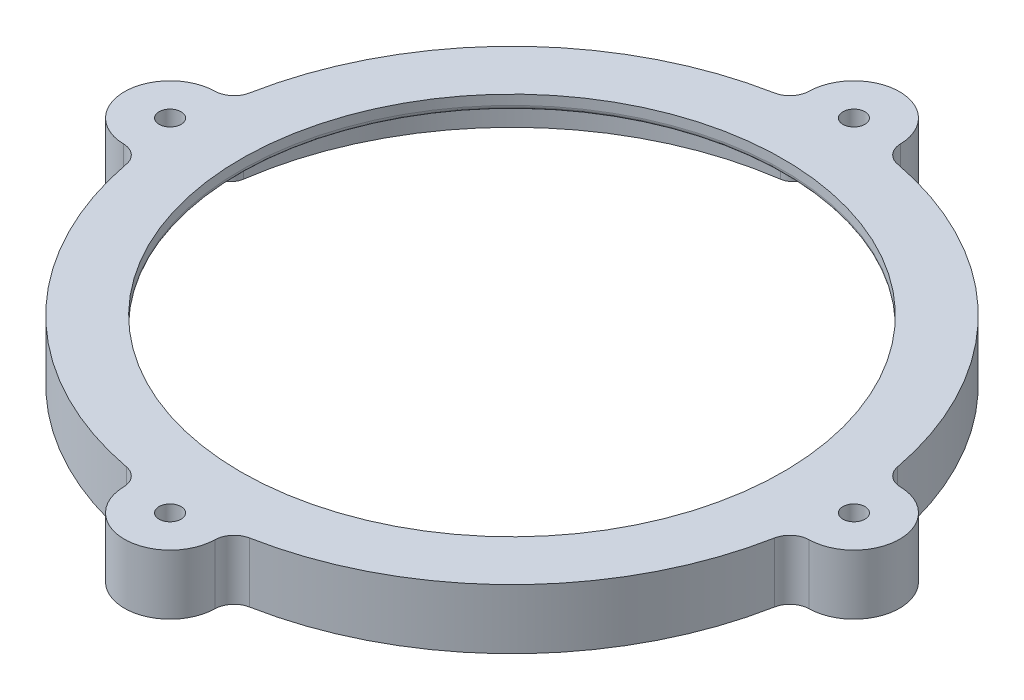
SolidWorks part; units mm, degrees
ref_plane "Front Plane" through (0, 0, 0) normal (0, 0, 1) x (1, 0, 0)
ref_plane "Top Plane" through (0, 0, 0) normal (0, 1, 0) x (1, 0, 0)
ref_plane "Right Plane" through (0, 0, 0) normal (1, 0, 0) x (0, 0, -1)
sketch "Sketch1" plane through (0, 0, 0) normal (0, 0, 1) x (1, 0, 0)
  line L0 (64.5, 0) -> (64.5, 1.75)
  line L1 (64.5, 1.75) -> (55.5, 1.75)
  line L2 (55.5, 1.75) -> (55.5, 4.75)
  line L3 (55.5, 4.75) -> (67.5, 4.75)
  line L4 (67.5, 4.75) -> (67.5, 0)
  line L5 (67.5, 0) -> (64.5, 0)
  line L6 (0, 4.75) -> (0, 0) construction
  dimension "D1" = 3
  dimension "D2" = 3
  dimension "D3" = 55.5
  dimension "D4" = 1.75
  dimension "D5" = 64.5
revolve "Revolve1" add sketch "Sketch1" angle 360 about L6
fillet "Fillet1" radius 1 1 edges at (0, 1.75, 55.5)
sketch "Sketch2" plane through (0, 4.75, 0) normal (0, 1, 0) x (1, 0, 0)
  line L0 (0, 0) -> (70, 0) construction
  line L1 (67.2328, 6) -> (70, 6)
  line L2 (70, -6) -> (67.2328, -6)
  line L3 (67.2328, -6) -> (67.2328, 6)
  circle A0 centre (0, 0) radius 67.5 construction
  arc A1 (70, 6) -> (70, -6) centre (70, 0) cw
  dimension "D1" = 6
  dimension "D2" = 70
extrude "Boss-Extrude1" add sketch "Sketch2" against normal up to surface (4.75 mm away) up to face at (0, 0, 67.5)
fillet "Fillet2" radius 2 2 edges at (67.2328, 2.375, 6) (67.2328, 2.375, -6)
hole_wizard "M4 Clearance Hole1" positions "Sketch7" profile "Sketch8" hole size "M4" standard "ANSI Metric" end condition through all
sketch "Sketch7" plane through (0, 4.75, 0) normal (0, 1, 0) x (1, 0, 0)
  point P0 (70, 0)
sketch "Sketch8" plane through (70, 4.75, 0) normal (1, 0, 0) x (0, 0, 1)
  line L0 (0, 0) -> (0, 4.75)
  line L1 (0, 4.75) -> (2.25, 4.75)
  line L2 (2.25, 4.75) -> (2.25, 0)
  line L5 (2.25, 0) -> (0, 0)
  line L11 (0, -6.35) -> (0, 107.95) construction
  dimension "Thru Hole Dia." = 4.5
  dimension "Thru Hole Depth" = 4.75
pattern_circular "CirPattern3" count 4 over 360 about axis through (0, 0, 0) along (0, 1, 0) of "Boss-Extrude1", "Fillet2", "M4 Clearance Hole1"
sketch "Sketch9" plane through (0, 0, 0) normal (0, -1, 0) x (1, 0, 0)
  line L4 (6, 69.038) -> (6, 70) construction
  line L11 (6.35, 70) -> (6.35, 64.1867)
  line L12 (-6.35, 70) -> (-6.35, 64.1867)
  line L13 (9.35, 70) -> (9.35, 66.8493)
  line L14 (-9.35, 70) -> (-9.35, 66.8493)
  line L15 (-70, 9.35) -> (-66.8493, 9.35)
  line L16 (-70, -9.35) -> (-66.8493, -9.35)
  line L19 (70, -9.35) -> (66.8493, -9.35)
  line L20 (70, 9.35) -> (66.8493, 9.35)
  line L23 (9.35, -70) -> (9.35, -66.8493)
  line L24 (-9.35, -70) -> (-9.35, -66.8493)
  line L56 (6.35, 69.038) -> (6.35, 70)
  line L57 (-6.35, 70) -> (-6.35, 69.038)
  line L58 (-69.038, 6.35) -> (-70, 6.35)
  line L59 (-70, -6.35) -> (-69.038, -6.35)
  line L60 (-6.35, -69.038) -> (-6.35, -70)
  line L61 (6.35, -70) -> (6.35, -69.038)
  line L62 (69.038, -6.35) -> (70, -6.35)
  line L63 (70, 6.35) -> (69.038, 6.35)
  line L66 (-64.1867, 6.35) -> (-70, 6.35)
  line L67 (-70, -6.35) -> (-64.1867, -6.35)
  line L68 (-6.35, -64.1867) -> (-6.35, -70)
  line L69 (6.35, -70) -> (6.35, -64.1867)
  line L70 (64.1867, -6.35) -> (70, -6.35)
  line L71 (70, 6.35) -> (64.1867, 6.35)
  arc A0 (7.7698, -67.0513) -> (67.0513, -7.7698) centre (0, 0) ccw construction
  arc A1 (67.0513, 7.7698) -> (7.7698, 67.0513) centre (0, 0) ccw construction
  arc A2 (66.8493, 9.35) -> (9.35, 66.8493) centre (0, 0) ccw
  arc A3 (-7.4245, -64.0713) -> (-6.35, -64.1867) centre (0, 0) ccw
  arc A4 (-9.35, 66.8493) -> (-66.8493, 9.35) centre (0, 0) ccw
  arc A5 (-66.8493, -9.35) -> (-9.35, -66.8493) centre (0, 0) ccw
  arc A7 (9.35, -66.8493) -> (66.8493, -9.35) centre (0, 0) ccw
  arc A8 (-64.0713, -7.4245) -> (-7.4245, -64.0713) centre (0, 0) ccw
  arc A13 (-67.0513, -7.7698) -> (-7.7698, -67.0513) centre (0, 0) ccw construction
  arc A14 (7.4245, 64.0713) -> (6.35, 64.1867) centre (0, 0) ccw
  arc A15 (-7.7698, 67.0513) -> (-67.0513, 7.7698) centre (0, 0) ccw construction
  arc A16 (64.1867, 6.35) -> (64.0713, 7.4245) centre (0, 0) ccw
  arc A17 (-6.35, 64.1867) -> (-64.1867, 6.35) centre (0, 0) ccw
  arc A18 (6.35, -64.1867) -> (64.1867, -6.35) centre (0, 0) ccw
  arc A19 (-64.1867, -6.35) -> (-64.0713, -7.4245) centre (0, 0) ccw
  arc A45 (9.35, 70) -> (-9.35, 70) centre (0, 70) ccw
  arc A46 (-70, 9.35) -> (-70, -9.35) centre (-70, 0) ccw
  arc A47 (-9.35, -70) -> (9.35, -70) centre (0, -70) ccw
  arc A48 (70, -9.35) -> (70, 9.35) centre (70, 0) ccw
  circle A49 centre (0, 0) radius 64.5 construction
  arc A50 (64.0713, 7.4245) -> (7.4245, 64.0713) centre (0, 0) ccw
  arc A61 (67.399, 7.8101) -> (7.8101, 67.399) centre (0, 0) ccw
  arc A62 (6.35, 69.038) -> (7.8101, 67.399) centre (8, 69.038) ccw
  arc A63 (6.35, 70) -> (-6.35, 70) centre (0, 70) ccw
  arc A64 (-7.8101, 67.399) -> (-6.35, 69.038) centre (-8, 69.038) ccw
  arc A65 (-7.8101, 67.399) -> (-67.399, 7.8101) centre (0, 0) ccw
  arc A66 (-69.038, 6.35) -> (-67.399, 7.8101) centre (-69.038, 8) ccw
  arc A67 (-70, 6.35) -> (-70, -6.35) centre (-70, 0) ccw
  arc A68 (-67.399, -7.8101) -> (-69.038, -6.35) centre (-69.038, -8) ccw
  arc A69 (-67.399, -7.8101) -> (-7.8101, -67.399) centre (0, 0) ccw
  arc A70 (-6.35, -69.038) -> (-7.8101, -67.399) centre (-8, -69.038) ccw
  arc A71 (-6.35, -70) -> (6.35, -70) centre (0, -70) ccw
  arc A72 (7.8101, -67.399) -> (6.35, -69.038) centre (8, -69.038) ccw
  arc A73 (7.8101, -67.399) -> (67.399, -7.8101) centre (0, 0) ccw
  arc A74 (69.038, -6.35) -> (67.399, -7.8101) centre (69.038, -8) ccw
  arc A75 (70, -6.35) -> (70, 6.35) centre (70, 0) ccw
  arc A76 (67.399, 7.8101) -> (69.038, 6.35) centre (69.038, 8) ccw
  arc A79 (6.35, 70) -> (-6.35, 70) centre (0, 70) ccw
  arc A83 (-70, 6.35) -> (-70, -6.35) centre (-70, 0) ccw
  arc A87 (-6.35, -70) -> (6.35, -70) centre (0, -70) ccw
  arc A91 (70, -6.35) -> (70, 6.35) centre (70, 0) ccw
  dimension "D3" = 1.4245
  dimension "D4" = 58.0713
  dimension "D5" = 13.4245
  dimension "D6" = 70.0713
  dimension "D1" = 0.35
  dimension "D2" = 3
extrude "Boss-Extrude2" add sketch "Sketch9" along normal up to vertex
sketch "Sketch10" plane through (0, 4.75, 0) normal (0, 1, 0) x (1, 0, 0)
  line L6 (9.35, -70) -> (9.35, -66.8493)
  line L8 (6.35, -67.9078) -> (6.35, -70)
  line L9 (-6.35, -70) -> (-6.35, -67.9078)
  line L11 (-9.35, -66.8493) -> (-9.35, -70)
  line L12 (9.35, -70) -> (9.35, -66.8493)
  line L17 (-9.35, -66.8493) -> (-9.35, -70)
  line L18 (-70, -9.35) -> (-66.8493, -9.35)
  line L20 (-67.9078, -6.35) -> (-70, -6.35)
  line L21 (-70, 6.35) -> (-67.9078, 6.35)
  line L23 (-66.8493, 9.35) -> (-70, 9.35)
  line L24 (-70, -9.35) -> (-66.8493, -9.35)
  line L29 (-66.8493, 9.35) -> (-70, 9.35)
  line L31 (66.8493, -9.35) -> (70, -9.35)
  line L32 (70, 9.35) -> (66.8493, 9.35)
  line L34 (67.9078, 6.35) -> (70, 6.35)
  line L35 (70, -6.35) -> (67.9078, -6.35)
  line L37 (66.8493, -9.35) -> (70, -9.35)
  line L38 (70, 9.35) -> (66.8493, 9.35)
  line L42 (-9.35, 70) -> (-9.35, 66.8493)
  line L44 (-6.35, 67.9078) -> (-6.35, 70)
  line L45 (6.35, 70) -> (6.35, 67.9078)
  line L47 (9.35, 66.8493) -> (9.35, 70)
  line L48 (-9.35, 70) -> (-9.35, 66.8493)
  line L53 (9.35, 66.8493) -> (9.35, 70)
  circle A0 centre (0, 70) radius 2.25 construction
  circle A1 centre (-70, 0) radius 2.25 construction
  circle A2 centre (70, 0) radius 2.25 construction
  circle A3 centre (0, -70) radius 2.25 construction
  circle A4 centre (0, 70) radius 2.25
  circle A5 centre (-70, 0) radius 2.25
  arc A6 (7.7698, -67.0513) -> (9.35, -66.8493) centre (0, 0) ccw
  arc A7 (-6.35, -67.9078) -> (-7.7698, -67.0513) centre (-8, -69.038) ccw
  arc A8 (-6.35, -70) -> (6.35, -70) centre (0, -70) ccw
  arc A9 (-6.35, -67.9078) -> (-7.7698, -67.0513) centre (-8, -69.038) ccw
  arc A10 (-9.35, -66.8493) -> (-7.7698, -67.0513) centre (0, 0) ccw
  arc A11 (-9.35, -70) -> (9.35, -70) centre (0, -70) ccw
  arc A12 (7.7698, -67.0513) -> (9.35, -66.8493) centre (0, 0) ccw
  arc A16 (-9.35, -66.8493) -> (7.7698, -67.0513) centre (0, 0) ccw
  arc A17 (-9.35, -70) -> (9.35, -70) centre (0, -70) ccw
  arc A18 (-67.0513, -7.7698) -> (-66.8493, -9.35) centre (0, 0) ccw
  arc A19 (-67.9078, 6.35) -> (-67.0513, 7.7698) centre (-69.038, 8) ccw
  arc A20 (-70, 6.35) -> (-70, -6.35) centre (-70, 0) ccw
  arc A21 (-67.9078, 6.35) -> (-67.0513, 7.7698) centre (-69.038, 8) ccw
  arc A22 (-66.8493, 9.35) -> (-67.0513, 7.7698) centre (0, 0) ccw
  arc A23 (-70, 9.35) -> (-70, -9.35) centre (-70, 0) ccw
  arc A24 (-67.0513, 7.7698) -> (-66.8493, -9.35) centre (0, 0) ccw
  arc A28 (-66.8493, 9.35) -> (-67.0513, 7.7698) centre (0, 0) ccw
  arc A29 (-70, 9.35) -> (-70, -9.35) centre (-70, 0) ccw
  arc A30 (66.8493, -9.35) -> (67.0513, -7.7698) centre (0, 0) ccw
  arc A31 (70, -9.35) -> (70, 9.35) centre (70, 0) ccw
  arc A32 (67.0513, 7.7698) -> (66.8493, 9.35) centre (0, 0) ccw
  arc A33 (67.9078, -6.35) -> (67.0513, -7.7698) centre (69.038, -8) ccw
  arc A34 (70, -6.35) -> (70, 6.35) centre (70, 0) ccw
  arc A35 (67.9078, -6.35) -> (67.0513, -7.7698) centre (69.038, -8) ccw
  arc A36 (66.8493, -9.35) -> (67.0513, -7.7698) centre (0, 0) ccw
  arc A37 (70, -9.35) -> (70, 9.35) centre (70, 0) ccw
  arc A38 (67.0513, -7.7698) -> (66.8493, 9.35) centre (0, 0) ccw
  arc A42 (-7.7698, 67.0513) -> (-9.35, 66.8493) centre (0, 0) ccw
  arc A43 (6.35, 67.9078) -> (7.7698, 67.0513) centre (8, 69.038) ccw
  arc A44 (6.35, 70) -> (-6.35, 70) centre (0, 70) ccw
  arc A45 (6.35, 67.9078) -> (7.7698, 67.0513) centre (8, 69.038) ccw
  arc A46 (9.35, 66.8493) -> (7.7698, 67.0513) centre (0, 0) ccw
  arc A47 (9.35, 70) -> (-9.35, 70) centre (0, 70) ccw
  arc A48 (7.7698, 67.0513) -> (-9.35, 66.8493) centre (0, 0) ccw
  arc A52 (9.35, 66.8493) -> (7.7698, 67.0513) centre (0, 0) ccw
  arc A53 (9.35, 70) -> (-9.35, 70) centre (0, 70) ccw
  circle A54 centre (70, 0) radius 2.25
  circle A55 centre (0, -70) radius 2.25
  arc A62 (7.7698, -67.0513) -> (6.35, -67.9078) centre (8, -69.038) ccw
  arc A63 (7.7698, -67.0513) -> (6.35, -67.9078) centre (8, -69.038) ccw
  arc A64 (-67.0513, -7.7698) -> (-67.9078, -6.35) centre (-69.038, -8) ccw
  arc A65 (-67.0513, -7.7698) -> (-67.9078, -6.35) centre (-69.038, -8) ccw
  arc A66 (67.0513, 7.7698) -> (67.9078, 6.35) centre (69.038, 8) ccw
  arc A67 (67.0513, 7.7698) -> (67.9078, 6.35) centre (69.038, 8) ccw
  arc A68 (-7.7698, 67.0513) -> (-6.35, 67.9078) centre (-8, 69.038) ccw
  arc A69 (-7.7698, 67.0513) -> (-6.35, 67.9078) centre (-8, 69.038) ccw
  dimension "D1" = 0
  dimension "D2" = 0
  dimension "D3" = 0
  dimension "D4" = 0
extrude "Boss-Extrude3" add sketch "Sketch10" against normal up to surface (4.75 mm away) contours A24 L24 A29 L29 A28 | A5 | A4 | A48 L48 A53 L53 A52 | A17 L12 A12 A16 L17 | A55 | A37 L38 A38 A36 L37 | A54 up to face at (0, 0, -69.9018)
fillet "Fillet3" radius 4 8 edges at (9.35, -1.375, -66.8493) (-9.35, -1.375, -66.8493) (-66.8493, -1.375, -9.35) (-9.35, -1.375, 66.8493) (-66.8493, -1.375, 9.35) (9.35, -1.375, 66.8493) (66.8493, -1.375, 9.35) (66.8493, -1.375, -9.35)
fillet "Fillet4" radius 3 8 edges at (64.1867, -3.75, 6.35) (64.1867, -3.75, -6.35) (6.35, -3.75, -64.1867) (-6.35, -3.75, -64.1867) (-64.1867, -3.75, -6.35) (-64.1867, -3.75, 6.35) (-6.35, -3.75, 64.1867) (6.35, -3.75, 64.1867)
